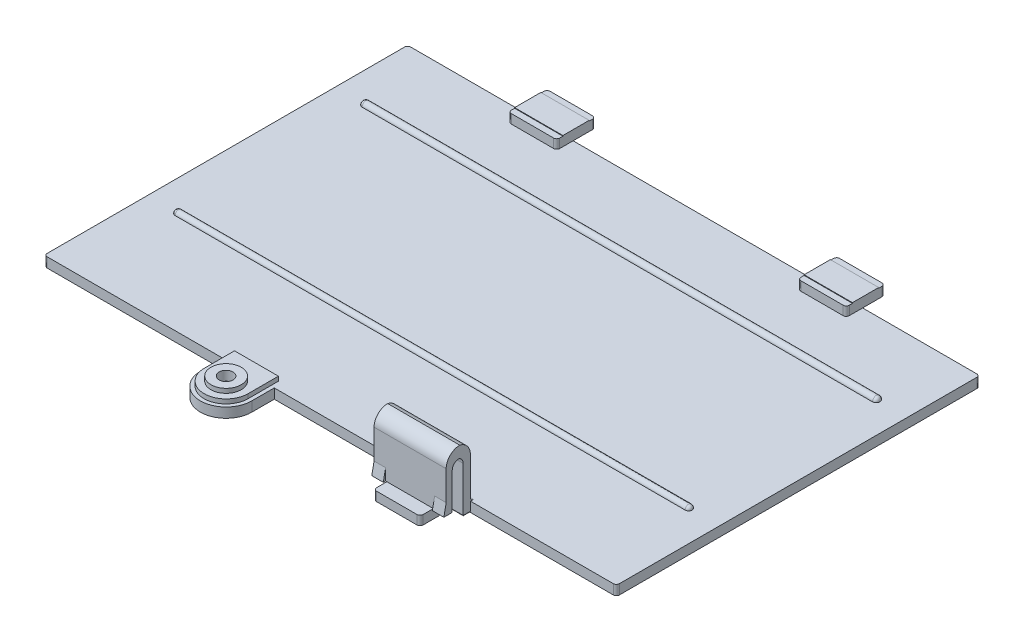
SolidWorks part; units mm, degrees
other "Marca1"
sketch "Croquis33" plane through (94.46, -0.1, -65.75) normal (0.331, -0.9283, -0.1692) x (0.9372, 0.3444, -0.056)
ref_plane "Alzado" through (0, 0, 0) normal (0, 0, 1) x (1, 0, 0)
ref_plane "Planta" through (0, 0, 0) normal (0, 1, 0) x (1, 0, 0)
ref_plane "Vista lateral" through (0, 0, 0) normal (1, 0, 0) x (0, 0, -1)
sketch "Croquis1" plane through (0, 0, 0) normal (0, 1, 0) x (1, 0, 0)
  line L0 (0, 0) -> (0, 60)
  line L1 (0, 60) -> (94.46, 60)
  line L2 (94.46, 60) -> (94.46, 0)
  line L3 (94.46, 0) -> (0, 0)
  dimension "D1" = 94.46
  dimension "D2" = 60
extrude "Saliente-Extruir1" add sketch "Croquis1" along normal blind 1.62
sketch "Croquis2" plane through (0, 1.62, 0) normal (0, 1, 0) x (1, 0, 0)
  line L0 (47.23, 60) -> (47.23, 47.39) construction
  line L1 (94.46, 60) -> (0, 60) construction
  line L2 (47.23, 47.39) -> (4.515, 47.39) construction
  line L3 (4.515, 47.39) -> (4.515, 48.64)
  line L4 (4.515, 48.64) -> (89.945, 48.64)
  line L5 (89.945, 48.64) -> (89.945, 47.39)
  line L6 (89.945, 47.39) -> (4.515, 47.39)
  dimension "D1" = 12.61
  dimension "D2" = 42.715
  dimension "D3" = 1.25
  dimension "D4" = 85.43
extrude "Saliente-Extruir3" add sketch "Croquis2" along normal blind 0.7
sketch "Croquis5" plane through (4.515, 0, 0) normal (-1, 0, 0) x (0, 0, 1)
  line L0 (-48.64, 1.62) -> (-47.39, 1.62) construction
  line L2 (-48.64, 1.62) -> (-48.64, 2.32)
  line L3 (-48.64, 2.32) -> (-47.39, 2.32)
  line L4 (-47.39, 2.32) -> (-47.39, 1.62)
  arc A0 (-47.39, 1.62) -> (-48.64, 1.62) centre (-48.015, 1.62) ccw
extrude "Cortar-Extruir2" cut sketch "Croquis5" against normal up to next
fillet "Redondeo2" radius 0.575 1 edges at (89.945, 2.245, -48.015)
fillet "Redondeo3" radius 0.575 1 edges at (4.515, 2.245, -48.015)
sketch "Croquis7" plane through (0, 1.62, 0) normal (0, 1, 0) x (1, 0, 0)
  line L0 (47.23, 0) -> (47.23, 17.6) construction
  line L1 (0, 0) -> (94.46, 0) construction
  line L2 (47.23, 17.6) -> (4.58, 17.6) construction
  line L3 (4.58, 17.6) -> (4.58, 16.45)
  line L4 (4.58, 16.45) -> (89.945, 16.45)
  line L5 (89.945, 16.45) -> (89.945, 17.6)
  line L6 (89.945, 17.6) -> (4.58, 17.6)
  dimension "D1" = 17.6
  dimension "D2" = 42.65
  dimension "D3" = 1.15
extrude "Saliente-Extruir4" add sketch "Croquis7" along normal blind 0.7
sketch "Croquis8" plane through (4.58, 0, 0) normal (-1, 0, 0) x (0, 0, 1)
  line L0 (-17.6, 1.62) -> (-16.45, 1.62) construction
  line L1 (-17.6, 1.62) -> (-17.6, 2.32)
  line L2 (-17.6, 2.32) -> (-16.45, 2.32)
  line L3 (-16.45, 2.32) -> (-16.45, 1.62)
  arc A0 (-16.45, 1.62) -> (-17.6, 1.62) centre (-17.025, 1.62) ccw
extrude "Cortar-Extruir3" cut sketch "Croquis8" against normal up to next
fillet "Redondeo4" radius 0.575 1 edges at (4.58, 2.195, -17.025)
fillet "Redondeo5" radius 0.575 1 edges at (89.945, 2.195, -17.025)
sketch "Croquis9" plane through (0, 1.62, 0) normal (0, 1, 0) x (1, 0, 0)
  line L0 (47.23, 60) -> (47.23, 57.5) construction
  line L1 (94.46, 60) -> (0, 60) construction
  line L2 (94.46, 60) -> (75.12, 60) construction
  line L3 (0, 60) -> (19.34, 60) construction
  line L4 (19.34, 63.68) -> (19.34, 57.29)
  line L5 (19.34, 63.68) -> (27.32, 63.68)
  line L6 (27.32, 63.68) -> (27.32, 57.29)
  line L7 (27.32, 57.29) -> (19.34, 57.29)
  line L9 (75.12, 63.68) -> (67.14, 63.68)
  line L10 (67.14, 63.68) -> (67.14, 57.29)
  line L11 (67.14, 57.29) -> (75.12, 57.29)
  line L12 (75.12, 57.29) -> (75.12, 63.68)
  dimension "D1" = 2.5
  dimension "D2" = 19.34
  dimension "D3" = 19.34
  dimension "D4" = 3.68
  dimension "D5" = 7.98
  dimension "D6" = 6.39
  dimension "D7" = 3.68
extrude "Saliente-Extruir6" add sketch "Croquis9" along normal blind 1.6 contours L4 L7 L6 L5 | L9 L10 L11 L12
sketch "Croquis10" plane through (0, 3.22, 0) normal (0, 1, 0) x (1, 0, 0)
  line L0 (19.34, 63.68) -> (19.34, 62.65)
  line L1 (19.34, 63.68) -> (19.34, 57.29) construction
  line L2 (19.34, 62.65) -> (27.32, 62.65)
  line L3 (27.32, 63.68) -> (27.32, 57.29) construction
  line L4 (27.32, 62.65) -> (27.32, 63.68)
  line L5 (27.32, 63.68) -> (19.34, 63.68)
  line L6 (19.34, 57.29) -> (19.34, 58.32)
  line L7 (19.34, 58.32) -> (27.32, 58.32)
  line L8 (27.32, 58.32) -> (27.32, 57.29)
  line L9 (27.32, 57.29) -> (19.34, 57.29)
  dimension "D1" = 1.03
extrude "Cortar-Extruir4" cut sketch "Croquis10" against normal blind 0.1
fillet "Redondeo7" radius 0.5 1 edges at (19.34, 2.37, -63.68)
fillet "Redondeo8" radius 0.5 3 edges at (27.32, 2.37, -63.68) (27.32, 2.37, -57.29) (19.34, 2.37, -57.29)
sketch "Croquis11" plane through (0, 3.22, 0) normal (0, 1, 0) x (1, 0, 0)
  line L0 (27.32, 62.65) -> (75.12, 62.65) construction
  line L1 (67.14, 63.68) -> (67.14, 62.65)
  line L2 (67.14, 63.68) -> (67.14, 57.29) construction
  line L3 (67.14, 62.65) -> (75.12, 62.65)
  line L4 (75.12, 62.65) -> (75.12, 63.68)
  line L5 (75.12, 63.68) -> (67.14, 63.68)
  line L6 (67.14, 57.29) -> (67.14, 58.32)
  line L7 (67.14, 60) -> (67.14, 57.29) construction
  line L8 (67.14, 58.32) -> (75.12, 58.32)
  line L9 (75.12, 57.29) -> (75.12, 60) construction
  line L10 (75.12, 58.32) -> (75.12, 57.29)
  line L11 (75.12, 57.29) -> (67.14, 57.29)
extrude "Cortar-Extruir5" cut sketch "Croquis11" against normal blind 0.1
fillet "Redondeo10" radius 0.5 1 edges at (75.12, 2.37, -57.29)
fillet "Redondeo11" radius 0.5 1 edges at (67.14, 2.37, -57.29)
fillet "Redondeo13" radius 0.5 1 edges at (67.14, 2.37, -63.68)
fillet "Redondeo15" radius 0.5 1 edges at (75.12, 2.37, -63.68)
sketch "Croquis12" plane through (0, 1.62, 0) normal (0, 1, 0) x (1, 0, 0)
  line L0 (29.5, 0) -> (37.98, 0) construction
  line L1 (0, 0) -> (94.46, 0) construction
  line L3 (37.98, 1.3) -> (29.5, 1.3)
  line L4 (29.5, 1.3) -> (29.5, -3.71)
  line L6 (37.98, -3.71) -> (37.98, 1.3)
  arc A0 (29.5, -3.71) -> (37.98, -3.71) centre (33.74, -3.71) ccw
  dimension "D1" = 29.5
  dimension "D2" = 8.48
  dimension "D3" = 1.3
extrude "Saliente-Extruir8" add sketch "Croquis12" along normal blind 1.48 and the other way blind 1.62
sketch "Croquis14" plane through (0, 3.1, 0) normal (0, 1, 0) x (1, 0, 0)
  line L0 (30.115, 1.3) -> (30.115, -3.71)
  line L1 (33.74, 1.3) -> (30.115, 1.3) construction
  line L2 (37.98, 1.3) -> (29.5, 1.3) construction
  line L3 (33.74, 1.3) -> (37.365, 1.3) construction
  line L4 (37.365, 1.3) -> (37.365, -3.71)
  line L6 (37.98, -3.71) -> (37.98, 1.3)
  line L7 (37.98, 1.3) -> (37.365, 1.3)
  line L8 (30.115, 1.3) -> (29.5, 1.3)
  line L9 (29.5, 1.3) -> (29.5, -3.71)
  arc A0 (29.5, -3.71) -> (37.98, -3.71) centre (33.74, -3.71) ccw
  arc A1 (30.115, -3.71) -> (37.365, -3.71) centre (33.74, -3.71) ccw
  dimension "D1" = 3.625
extrude "Cortar-Extruir8" cut sketch "Croquis14" against normal blind 1.48
sketch "Croquis16" plane through (0, 3.1, 0) normal (0, 1, 0) x (1, 0, 0)
  line L0 (30.115, -3.71) -> (30.115, 1.3)
  line L1 (30.115, -3.71) -> (30.115, 1.3) construction
  line L2 (30.115, 1.3) -> (37.365, 1.3) construction
  line L3 (30.115, 1.3) -> (37.365, 1.3)
  line L4 (37.365, 1.3) -> (37.365, -3.71)
  arc A0 (30.115, -3.71) -> (37.365, -3.71) centre (33.74, -3.71) ccw
extrude "Cortar-Extruir9" cut sketch "Croquis16" against normal blind 0.76
sketch "Croquis17" plane through (0, 2.34, 0) normal (0, 1, 0) x (1, 0, 0)
  circle A0 centre (33.74, -3.71) radius 2.5
  dimension "D1" = 5
extrude "Saliente-Extruir9" add sketch "Croquis17" along normal blind 0.72
sketch "Croquis18" plane through (0, 3.06, 0) normal (0, 1, 0) x (1, 0, 0)
  circle A0 centre (33.74, -3.71) radius 1.15
  dimension "D1" = 2.3
extrude "Cortar-Extruir11" cut sketch "Croquis18" against normal through all
sketch "Croquis20" plane through (0, 0, 0) normal (0, -1, 0) x (1, 0, 0)
  circle A0 centre (33.74, 3.71) radius 2.36
  dimension "D1" = 4.72
extrude "Cortar-Extruir12" cut sketch "Croquis20" against normal blind 1.5
sketch "Croquis21" plane through (0, 1.62, 0) normal (0, 1, 0) x (1, 0, 0)
  line L0 (94.46, 0) -> (70.36, 0) construction
  line L1 (37.98, 0) -> (94.46, 0) construction
  line L2 (70.36, 0) -> (58.46, 0)
  line L3 (58.46, 0) -> (58.46, -1.18)
  line L4 (58.46, -1.18) -> (70.36, -1.18)
  line L5 (70.36, -1.18) -> (70.36, 0)
  dimension "D1" = 36
  dimension "D2" = 11.9
  dimension "D3" = 1.18
extrude "Saliente-Extruir10" add sketch "Croquis21" along normal blind 8.88 and the other way up to vertex (1.62 mm away) other way up to point (37.98, 0, 0)
sketch "Croquis22" plane through (0, 0, 1.18) normal (0, 0, 1) x (1, 0, 0)
  line L0 (58.46, 10.5) -> (58.46, 8.64)
  line L1 (58.46, 0) -> (58.46, 10.5) construction
  line L2 (58.46, 10.5) -> (70.36, 10.5)
  line L3 (70.36, 10.5) -> (70.36, 8.64)
  line L4 (70.36, 0) -> (70.36, 10.5) construction
  line L5 (70.36, 8.64) -> (58.46, 8.64)
  dimension "D1" = 1.86
extrude "Saliente-Extruir11" add sketch "Croquis22" along normal blind 2.82
sketch "Croquis23" plane through (0, 8.64, 0) normal (0, -1, 0) x (1, 0, 0)
  line L0 (58.46, 4) -> (58.46, 3)
  line L1 (58.46, 4) -> (58.46, 1.18) construction
  line L2 (58.46, 3) -> (70.36, 3)
  line L3 (70.36, 4) -> (70.36, 1.18) construction
  line L4 (70.36, 3) -> (70.36, 4)
  line L5 (70.36, 4) -> (58.46, 4)
  dimension "D1" = 1
extrude "Saliente-Extruir12" add sketch "Croquis23" along normal up to surface (8.64 mm away) up to face at (33.74, 0, 1.35)
fillet "Redondeo16" radius 2.25 1 edges at (64.41, 10.5, 4)
fillet "Redondeo18" radius 0.5 1 edges at (64.41, 1.62, 0)
fillet "Redondeo19" radius 2.25 1 edges at (64.41, 10.5, 0)
fillet "Redondeo21" radius 1.125 1 edges at (64.41, 8.64, 3)
fillet "Redondeo22" radius 1.125 1 edges at (64.41, 8.64, 1.18)
sketch "Croquis24" plane through (0, 0, 4) normal (0, 0, 1) x (1, 0, 0)
  line L0 (64.41, 0) -> (64.41, 1.826) construction
  line L1 (70.36, 0) -> (58.46, 0) construction
  line L2 (64.41, 0) -> (60.57, 0) construction
  line L3 (64.41, 0) -> (68.25, 0) construction
  line L4 (60.57, 0) -> (60.57, 1.5)
  line L5 (60.57, 1.5) -> (68.25, 1.5)
  line L6 (68.25, 1.5) -> (68.25, 0)
  line L7 (60.57, 0) -> (68.25, 0)
  dimension "D1" = 3.84
  dimension "D2" = 1.5
extrude "Saliente-Extruir14" add sketch "Croquis24" along normal blind 2.2
sketch "Croquis26" plane through (0, 0, 4) normal (0, 0, 1) x (1, 0, 0)
  line L0 (60.57, 1.5) -> (58.46, 1.5)
  line L1 (58.46, 0) -> (58.46, 1.62) construction
  line L2 (58.46, 1.5) -> (58.46, 0)
  line L3 (58.46, 0) -> (60.57, 0)
  line L4 (60.57, 0) -> (60.57, 1.5)
  line L5 (68.25, 1.5) -> (68.25, 0)
  line L6 (68.25, 0) -> (68.25, 1.5) construction
  line L7 (68.25, 0) -> (70.36, 0)
  line L8 (70.36, 0) -> (70.36, 1.5)
  line L9 (70.36, 0) -> (70.36, 1.62) construction
  line L10 (70.36, 1.5) -> (68.25, 1.5)
extrude "Cortar-Extruir13" cut sketch "Croquis26" against normal up to next
fillet "Redondeo25" radius 0.5 1 edges at (68.25, 0.75, 6.2)
fillet "Redondeo26" radius 0.5 1 edges at (60.57, 0.75, 6.2)
sketch "Croquis27" plane through (0, 0, 4) normal (0, 0, 1) x (1, 0, 0)
  line L0 (70.36, 1.5) -> (70.36, 3.4)
  line L1 (70.36, 1.5) -> (70.36, 8.25) construction
  dimension "D1" = 1.9
sketch "Croquis28" plane through (70.36, 0, 0) normal (1, 0, 0) x (0, 0, -1)
  line L0 (-4, 1.5) -> (-4.38, 1.5)
  line L1 (-5.7, 1.5) -> (-4, 1.5) construction
  line L2 (-4, 1.5) -> (-4, 3.4)
  line L3 (-4, 1.5) -> (-4, 3.4) construction
  line L4 (-4.38, 1.5) -> (-4, 3.4)
  dimension "D1" = 0.38
  dimension "D2" = 1.9
extrude "Saliente-Extruir21" add sketch "Croquis28" against normal blind 1.9
sketch "Croquis29" plane through (58.46, 0, 0) normal (-1, 0, 0) x (0, 0, 1)
  line L0 (4, 1.5) -> (4.38, 1.5)
  line L1 (4, 1.5) -> (4, 3.4)
  line L2 (4, 8.25) -> (4, 1.5) construction
  line L3 (4, 3.4) -> (4.38, 1.5)
  dimension "D1" = 0.38
  dimension "D2" = 1.9
extrude "Saliente-Extruir22" add sketch "Croquis29" against normal blind 1.9
fillet "Redondeo27" radius 0.5 1 edges at (94.46, 0.81, 0)
fillet "Redondeo28" radius 0.5 1 edges at (94.46, 0.81, -60)
fillet "Redondeo29" radius 0.5 1 edges at (0, 0.81, -60)
fillet "Redondeo30" radius 0.5 1 edges at (0, 0.81, 0)
sketch "Croquis30" plane through (0, 0, 0) normal (0, -1, 0) x (1, 0, 0)
  line L0 (59.91, 0) -> (59.91, -4.02) construction
  line L1 (59.91, -4.02) -> (59.91, -5.02)
  line L2 (59.91, -5.02) -> (68.91, -5.02)
  line L3 (68.91, -5.02) -> (68.91, -4.02)
  line L4 (68.91, -4.02) -> (59.91, -4.02)
  line L5 (59.91, -5.02) -> (59.91, -6.02) construction
  line L6 (59.91, -6.02) -> (59.91, -7.02)
  line L7 (59.91, -7.02) -> (68.91, -7.02)
  line L8 (68.91, -7.02) -> (68.91, -6.02)
  line L9 (68.91, -6.02) -> (59.91, -6.02)
  line L10 (59.91, -7.02) -> (59.91, -8.02) construction
  line L11 (58.46, 1.18) -> (70.36, 1.18) construction
  line L12 (59.91, -8.02) -> (64.41, -10.92)
  line L13 (64.41, -10.92) -> (68.91, -8.02)
  line L14 (68.91, -8.02) -> (59.91, -8.02)
  line L15 (68.91, -5.02) -> (68.91, -6.02) construction
  line L16 (68.91, -7.02) -> (68.91, -8.02) construction
  line L17 (64.41, -8.02) -> (64.41, -10.92) construction
  line L18 (58.46, 0) -> (59.91, 0) construction
  line L19 (59.91, -3.02) -> (68.91, -3.02) construction
  line L20 (68.91, -3.02) -> (68.91, -4.02) construction
  line L21 (68.91, -3.02) -> (68.91, 0) construction
  line L22 (59.91, 0) -> (68.91, 0) construction
  line L23 (68.91, 0) -> (70.36, 0) construction
  text T0 "OPEN" font "Consolas" height 3
  dimension "D1" = 1
  dimension "D2" = 6.2
  dimension "D3" = 1
  dimension "D4" = 1
  dimension "D5" = 9
  dimension "D6" = 2.9
  dimension "D7" = 1
extrude "Saliente-Extruir23" add sketch "Croquis30" along normal blind 0.1
fillet "Redondeo31" radius 0.2 3 edges at (64.41, 0, 1.18) (70.36, 0, 0.59) (58.46, 0, 0.59)
sketch "Croquis31" plane through (0, 0, 0) normal (0, -1, 0) x (1, 0, 0)
  line L0 (56.66, 0) -> (56.66, -60) construction
  line L1 (37.98, 0) -> (58.66, 0) construction
  line L2 (93.96, -60) -> (0.5, -60) construction
  text T0 "MADE IN UPITTA" font "Consolas" height 3
  dimension "D1" = 2
extrude "Saliente-Extruir24" add sketch "Croquis31" along normal blind 0.1
sketch "Croquis32" plane through (0, 0, 0) normal (0, -1, 0) x (1, 0, 0)
  line L0 (47.23, 0) -> (47.23, -26.5) construction
  line L1 (47.23, -26.5) -> (45.43, -26.5)
  line L2 (47.23, -26.5) -> (47.23, -33.5)
  line L3 (47.23, -33.5) -> (45.43, -33.5)
  line L4 (45.43, -26.5) -> (45.43, -33.5)
  line L6 (47.23, -33.5) -> (47.23, -60) construction
  line L7 (93.96, -60) -> (0.5, -60) construction
  line L8 (37.98, 0) -> (58.66, 0) construction
  line L9 (37.43, 0) -> (37.43, -46.7) construction
  line L10 (37.43, -46.7) -> (37.43, -54.8) construction
  line L11 (37.43, -54.8) -> (37.43, -60) construction
  text T0 "2.4\r\nGHz" font "Consolas" height 2.5
  dimension "D1" = 7
  dimension "D2" = 1.8
  dimension "D3" = 8
  dimension "D4" = 8.1
  dimension "D5" = 5.2
extrude "Saliente-Extruir25" add sketch "Croquis32" along normal blind 0.1
